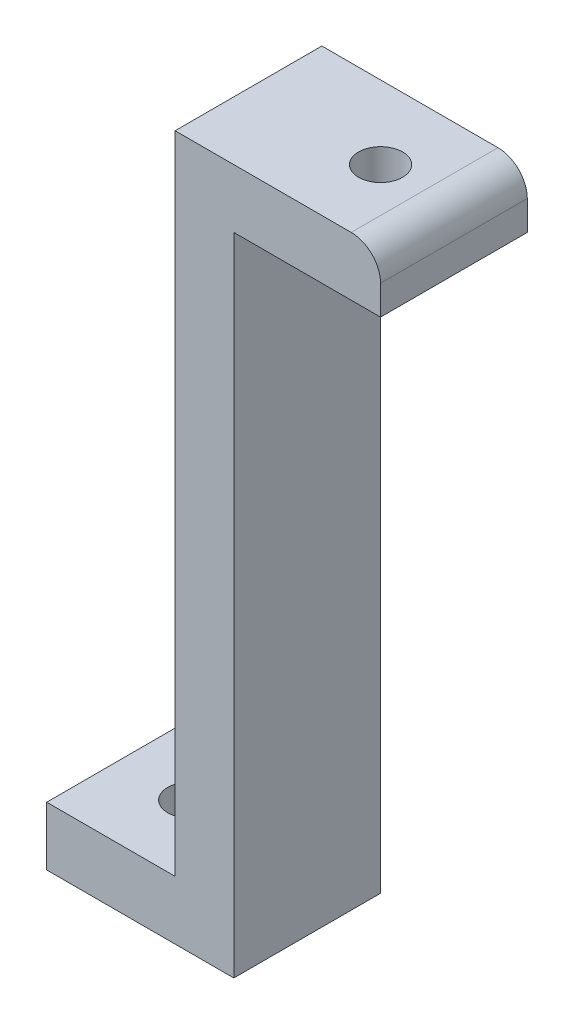
SolidWorks part; units mm, degrees
ref_plane "Front Plane" through (0, 0, 0) normal (0, 0, 1) x (1, 0, 0)
ref_plane "Top Plane" through (0, 0, 0) normal (0, 1, 0) x (1, 0, 0)
ref_plane "Right Plane" through (0, 0, 0) normal (1, 0, 0) x (0, 0, -1)
sketch "Sketch1" plane through (0, 0, 0) normal (0, 0, 1) x (1, 0, 0)
  line L0 (0, 0) -> (-14, 0)
  line L1 (-14, 0) -> (-14, -44)
  line L2 (-14, -44) -> (-22.75, -44)
  line L3 (-22.75, -44) -> (-22.75, -48)
  line L4 (-22.75, -48) -> (-10, -48)
  line L5 (-10, -48) -> (-10, -4)
  line L6 (-10, -4) -> (0, -4)
  line L7 (0, -4) -> (0, 0)
  dimension "D1" = 4
  dimension "D2" = 4
  dimension "D3" = 4
  dimension "D4" = 44
  dimension "D5" = 12.75
  dimension "D6" = 10
extrude "Boss-Extrude1" add sketch "Sketch1" along normal blind 10
sketch "Sketch2" plane through (0, -44, 0) normal (0, 1, 0) x (1, 0, 0)
  line L0 (-22.75, -10) -> (-22.75, 0) construction
  circle A0 centre (-18, -5) radius 1.5
  point P4 (-22.75, -5)
  dimension "D1" = 3
  dimension "D2" = 4.75
  dimension "D3" = 0
extrude "Cut-Extrude1" cut sketch "Sketch2" against normal blind 10
sketch "Sketch3" plane through (0, -4, 0) normal (0, -1, 0) x (-1, 0, 0)
  line L0 (0, -10) -> (0, 0) construction
  line L2 (10, -10) -> (10, 0) construction
  circle A0 centre (5, -5) radius 1.5
  point P4 (0, -5)
  dimension "D1" = 3
  dimension "D2" = 0
  dimension "D3" = 5
extrude "Cut-Extrude2" cut sketch "Sketch3" against normal blind 10
fillet "Fillet1" radius 2 1 edges at (0, 0, 5)
